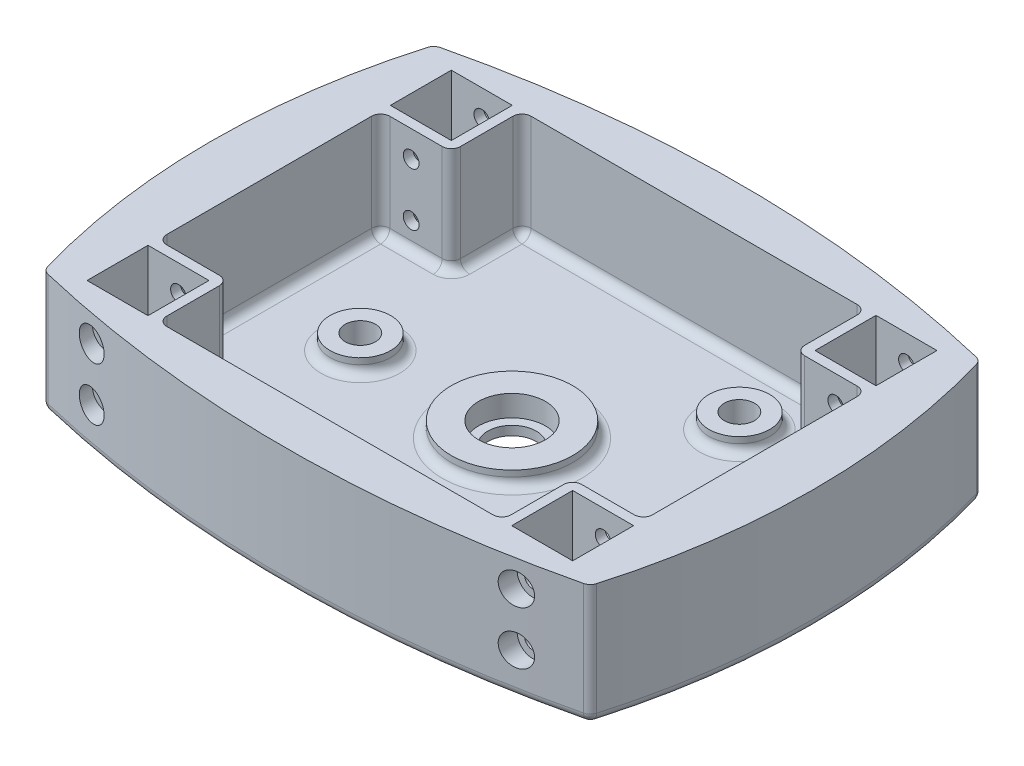
SolidWorks part; units mm, degrees
ref_plane "Front Plane" through (0, 0, 0) normal (0, 0, 1) x (1, 0, 0)
ref_plane "Top Plane" through (0, 0, 0) normal (0, 1, 0) x (1, 0, 0)
ref_plane "Right Plane" through (0, 0, 0) normal (1, 0, 0) x (0, 0, -1)
sketch "Sketch1" plane through (0, 0, 0) normal (0, 1, 0) x (1, 0, 0)
  line L0 (-140, 0) -> (0, 0) construction
  line L1 (-150.05, 10.05) -> (-129.95, 10.05)
  line L2 (-150.05, 10.05) -> (-150.05, -10.05)
  line L3 (-150.05, -10.05) -> (-129.95, -10.05)
  line L4 (-129.95, 10.05) -> (-129.95, -10.05)
  line L5 (-150.05, 10.05) -> (-129.95, -10.05) construction
  line L6 (-150.05, -10.05) -> (-129.95, 10.05) construction
  line L7 (-10.05, 10.05) -> (10.05, 10.05)
  line L8 (-10.05, 10.05) -> (-10.05, -10.05)
  line L9 (-10.05, -10.05) -> (10.05, -10.05)
  line L10 (10.05, 10.05) -> (10.05, -10.05)
  line L11 (-10.05, 10.05) -> (10.05, -10.05) construction
  line L12 (-10.05, -10.05) -> (10.05, 10.05) construction
  line L17 (-160, 14.2857) -> (-70, -50) construction
  line L18 (-150.05, -110.05) -> (-129.95, -110.05)
  line L23 (-150.05, -110.05) -> (-150.05, -89.95)
  line L24 (-150.05, -89.95) -> (-129.95, -89.95)
  line L25 (-129.95, -110.05) -> (-129.95, -89.95)
  line L26 (-150.05, -110.05) -> (-129.95, -89.95) construction
  line L27 (-150.05, -89.95) -> (-129.95, -110.05) construction
  line L28 (-10.05, -110.05) -> (10.05, -110.05)
  line L29 (-10.05, -110.05) -> (-10.05, -89.95)
  line L30 (-10.05, -89.95) -> (10.05, -89.95)
  line L31 (10.05, -110.05) -> (10.05, -89.95)
  line L32 (-10.05, -110.05) -> (10.05, -89.95) construction
  line L33 (-10.05, -89.95) -> (10.05, -110.05) construction
  line L35 (-70, -50) -> (20, -114.2857) construction
  line L37 (20, 14.2857) -> (-70, -50) construction
  line L38 (-70, -50) -> (-160, -114.2857) construction
  line L39 (-126.75, 10.05) -> (-126.75, -13.25)
  line L40 (-126.75, -13.25) -> (-150.05, -13.25)
  line L41 (-13.25, 10.05) -> (-13.25, -13.25)
  line L42 (-150.05, -86.75) -> (-126.75, -86.75)
  line L43 (-126.75, -86.75) -> (-126.75, -110.05)
  line L44 (-13.25, -13.25) -> (10.05, -13.25)
  line L45 (-13.25, -110.05) -> (-13.25, -86.75)
  line L46 (-13.25, -86.75) -> (10.05, -86.75)
  line L47 (10.05, -13.25) -> (10.05, -86.75)
  line L48 (-126.75, -110.05) -> (-13.25, -110.05)
  line L49 (-126.75, 10.05) -> (-13.25, 10.05)
  line L50 (-150.05, -13.25) -> (-150.05, -86.75)
  circle A0 centre (-70, -50) radius 8
  circle A2 centre (-120, -50) radius 5
  arc A5 (-160, 14.2857) -> (20, 14.2857) centre (-70, -354.9026) cw
  arc A6 (-160, -114.2857) -> (20, -114.2857) centre (-70, 254.9026) ccw
  arc A7 (-160, 14.2857) -> (-160, -114.2857) centre (55.6208, -50) ccw
  arc A8 (20, 14.2857) -> (20, -114.2857) centre (-195.6208, -50) cw
  circle A9 centre (-70, -50) radius 11
  circle A10 centre (-35, -10.05) radius 5
  circle A11 centre (-35, -89.95) radius 5
  circle A12 centre (-70, -50) radius 20
  circle A13 centre (-120, -50) radius 10
  circle A14 centre (-35, -10.05) radius 10
  circle A15 centre (-35, -89.95) radius 10
  point P0 (-140, 0)
  point P5 (0, 0)
  point P10 (0, -100)
  point P16 (-140, -100)
  dimension "D4" = 22
  dimension "D5" = 16
  dimension "D7" = 225
  dimension "D8" = 380
  dimension "D9" = 10
  dimension "D16" = 40
  dimension "D17" = 20
  dimension "D1" = 20.1
  dimension "D2" = 140
  dimension "D3" = 100
  dimension "D6" = 180
  dimension "D10" = 35
  dimension "D11" = 3.2
  dimension "D12" = 3.2
  dimension "D13" = 3.2
  dimension "D14" = 3.2
  dimension "D15" = 20
extrude "Boss-Extrude1" add sketch "Sketch1" along normal blind 40 contours A8 A5 A7 A6 A9 A10 A11 A2 L31 L28 L29 L30 L25 L18 L23 L24 L1 L4 L3 L2 L7 L10 L9 L8 region at (-70, 0, -22.6062)
extrude "Boss-Extrude2" add sketch "Sketch1<3>" along normal blind 5 contours L40 L50 L42 L43 L48 L45 L46 L47 L44 L41 L49 L39 A11 A10 A9 A2 region at (-70, 0, -8.0486)
sketch "Sketch1<3>" plane through (0, 0, 0) normal (0, 1, 0) x (1, 0, 0) same geometry as "Sketch1"
extrude "Boss-Extrude3" add sketch "Sketch1<4>" along normal blind 3 contours A9 A0 | L4 L1 L2 L3 | L18 L25 L24 L23 | L10 L7 L8 L9 | L28 L31 L30 L29 region at (-140, 0, 0) region at (0, 0, 0) region at (-140, 0, 100) region at (0, 0, 100) region at (-80.6889, 0, 50)
sketch "Sketch1<4>" plane through (0, 0, 0) normal (0, 1, 0) x (1, 0, 0) same geometry as "Sketch1"
sketch "Sketch2" plane through (0, 0, 13.25) normal (0, 0, 1) x (1, 0, 0)
  line L0 (-150.05, 40) -> (-129.95, 40) construction
  line L1 (-126.75, 40) -> (-150.05, 40) construction
  line L2 (-129.95, 40) -> (-129.95, 5) construction
  line L4 (-129.95, 40) -> (-129.95, 3) construction
  line L5 (-129.95, 5) -> (-150.05, 5) construction
  line L6 (-150.05, 40) -> (-150.05, 3) construction
  line L7 (-150.05, 5) -> (-150.05, 40) construction
  line L8 (-10.05, 40) -> (10.05, 40) construction
  line L9 (10.05, 40) -> (10.05, 5) construction
  line L10 (10.05, 5) -> (-10.05, 5) construction
  line L11 (-10.05, 5) -> (-10.05, 40) construction
  line L12 (-10.05, 40) -> (10.05, 22.5) construction
  line L13 (10.05, 40) -> (-10.05, 22.5) construction
  line L14 (10.05, 22.5) -> (-10.05, 5) construction
  line L15 (-10.05, 22.5) -> (10.05, 5) construction
  line L16 (-129.95, 40) -> (-150.05, 22.5) construction
  line L17 (-150.05, 22.5) -> (-129.95, 5) construction
  line L18 (-150.05, 5) -> (-129.95, 22.5) construction
  line L19 (-129.95, 22.5) -> (-150.05, 40) construction
  circle A0 centre (-140, 31.25) radius 2.6
  circle A1 centre (-140, 13.75) radius 2.6
  circle A2 centre (0, 31.25) radius 2.6
  circle A3 centre (0, 13.75) radius 2.6
  circle A4 centre (0, 13.75) radius 5.05
  circle A5 centre (0, 31.25) radius 5.05
  circle A6 centre (-140, 31.25) radius 5.05
  circle A7 centre (-140, 13.75) radius 5.05
  line M2 (-150.05, 5) -> (-126.75, 5)
  dimension "D1" = 5.2
  dimension "D2" = 10.1
extrude "Cut-Extrude1" cut sketch "Sketch2" against normal blind 62 contours A0 | A1 M2 | A6 A0 | A7 A1 M2 | A2 | A5 A2 | A3 | A4 A3 region at (-140, 31.25, 13.25) region at (-140, 13.75, 13.25) region at (0, 31.25, 13.25) region at (0, 13.75, 13.25) region at (-4.9072, 13.75, 13.25) region at (-4.9072, 31.25, 13.25) region at (-144.9072, 31.25, 13.25) region at (-144.9072, 13.75, 13.25)
extrude "Boss-Extrude4" add sketch "Sketch1<6>" along normal blind 10 contours A12 A9 | A13 A2 | A14 A10 | A15 A11 region at (-89.4343, 0, 50) region at (-129.7172, 0, 50) region at (-44.7172, 0, 10.05) region at (-44.7172, 0, 89.95)
sketch "Sketch1<6>" plane through (0, 0, 0) normal (0, 1, 0) x (1, 0, 0) same geometry as "Sketch1"
extrude "Boss-Extrude5" add sketch "Sketch2<3>" against normal blind 26.5
sketch "Sketch2<3>" plane through (0, 0, 13.25) normal (0, 0, 1) x (1, 0, 0) same geometry as "Sketch2"
extrude "Cut-Extrude2" cut sketch "Sketch2<4>" against normal up to surface (23.3 mm away) up to face at (-145.05, 13.75, -10.05)
sketch "Sketch2<4>" plane through (0, 0, 13.25) normal (0, 0, 1) x (1, 0, 0) same geometry as "Sketch2"
extrude "Boss-Extrude6" add sketch "Sketch2<5>" against normal up to surface (3.2 mm away) up to face at (-145.05, 13.75, 10.05)
sketch "Sketch2<5>" plane through (0, 0, 13.25) normal (0, 0, 1) x (1, 0, 0) same geometry as "Sketch2"
extrude "Cut-Extrude3" cut sketch "Sketch2<6>" along normal blind 127.2 contours A6 A0 | A7 A1 | A5 A2 | A4 A3 | A2 | A3 | A1 | A0 region at (-140, 31.25, 13.25) region at (-140, 13.75, 13.25) region at (0, 31.25, 13.25) region at (0, 13.75, 13.25) region at (-4.9072, 13.75, 13.25) region at (-4.9072, 31.25, 13.25) region at (-144.9072, 31.25, 13.25) region at (-144.9072, 13.75, 13.25)
sketch "Sketch2<6>" plane through (0, 0, 13.25) normal (0, 0, 1) x (1, 0, 0) same geometry as "Sketch2"
extrude "Boss-Extrude7" add sketch "Sketch2<7>" along normal blind 100 contours A7 A1 | A6 A0 | A4 A3 | A5 A2 region at (-4.9072, 13.75, 13.25) region at (-4.9072, 31.25, 13.25) region at (-144.9072, 31.25, 13.25) region at (-144.9072, 13.75, 13.25)
sketch "Sketch2<7>" plane through (0, 0, 13.25) normal (0, 0, 1) x (1, 0, 0) same geometry as "Sketch2"
extrude "Cut-Extrude4" cut sketch "Sketch2<8>" along normal up to surface (96.8 mm away) up to face at (-145.05, 31.25, 110.05)
sketch "Sketch2<8>" plane through (0, 0, 13.25) normal (0, 0, 1) x (1, 0, 0) same geometry as "Sketch2"
extrude "Boss-Extrude8" add sketch "Sketch2<9>" along normal up to surface (76.7 mm away) up to face at (-145.05, 31.25, 89.95)
sketch "Sketch2<9>" plane through (0, 0, 13.25) normal (0, 0, 1) x (1, 0, 0) same geometry as "Sketch2"
extrude "Cut-Extrude5" cut sketch "Sketch2<10>" along normal up to surface (73.5 mm away) contours A6 A0 | A0 | A7 A1 | A1 | A5 A2 | A2 | A3 | A4 A3 region at (-140, 31.25, 13.25) region at (-140, 13.75, 13.25) region at (0, 31.25, 13.25) region at (0, 13.75, 13.25) region at (-4.9072, 13.75, 13.25) region at (-4.9072, 31.25, 13.25) region at (-144.9072, 31.25, 13.25) region at (-144.9072, 13.75, 13.25) up to face at (-5.05, 13.75, 86.75)
sketch "Sketch2<10>" plane through (0, 0, 13.25) normal (0, 0, 1) x (1, 0, 0) same geometry as "Sketch2"
fillet "Fillet1" radius 3 36 edges at (-13.25, 5, 98.4) (-1.6, 5, 13.25) (-138.4, 5, 86.75) (-126.75, 5, 1.6) (-160, 20, -14.2857) (20, 20, 114.2857) (20, 20, -14.2857) (-70, 0, -25.0974) (29.3792, 0, 50) (-160, 20, 114.2857) (-169.3792, 0, 50) (-70, 0, 125.0974) (-13.25, 22.5, 110.05) (-1.6, 5, 86.75) (-13.25, 22.5, 86.75) (10.05, 22.5, 86.75) (10.05, 22.5, 13.25) (10.05, 5, 50) (-13.25, 22.5, 13.25) (-13.25, 5, 1.6) (-13.25, 22.5, -10.05) (-70, 5, 70) (-70, 5, 110.05) (-126.75, 5, 98.4) (-126.75, 22.5, 110.05) (-126.75, 22.5, 86.75) (-150.05, 22.5, 86.75) (-70, 5, -10.05) (-150.05, 5, 50) (-150.05, 22.5, 13.25) (-138.4, 5, 13.25) (-126.75, 22.5, 13.25) (-126.75, 22.5, -10.05) (-35, 5, 99.95) (-35, 5, 20.05) (-120, 5, 60)
